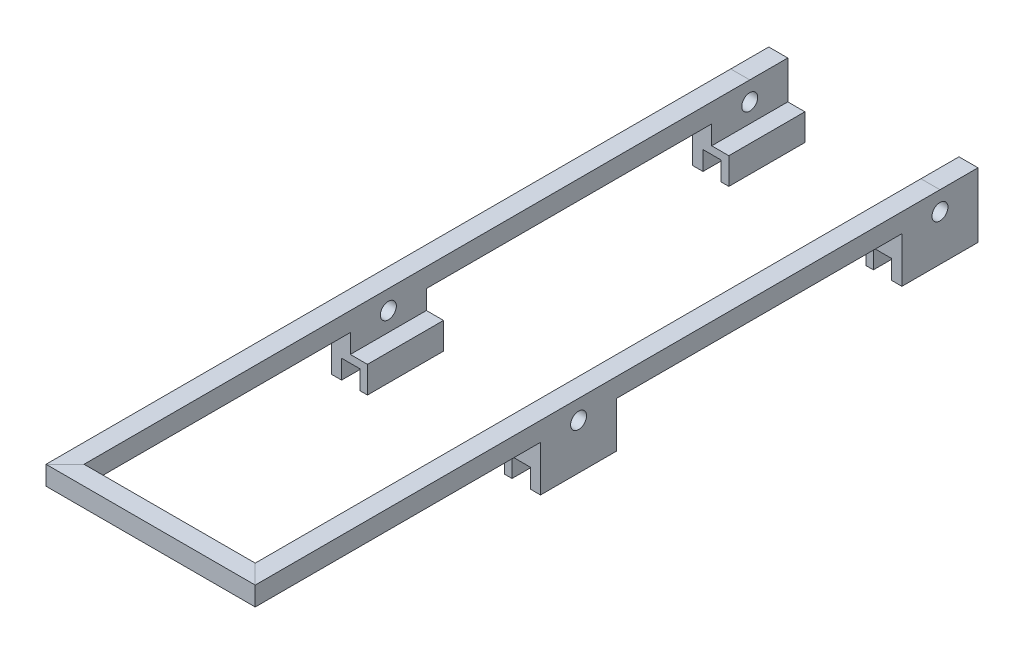
SolidWorks part; units mm, degrees
ref_plane "Front Plane" through (0, 0, 0) normal (0, 0, 1) x (1, 0, 0)
ref_plane "Top Plane" through (0, 0, 0) normal (0, 1, 0) x (1, 0, 0)
ref_plane "Right Plane" through (0, 0, 0) normal (1, 0, 0) x (0, 0, -1)
sketch "rail_path" plane through (0, 0, 0) normal (0, 1, 0) x (1, 0, 0)
  line L0 (28.575, 111.125) -> (28.575, 123.825)
  line L1 (-28.575, -111.125) -> (28.575, -111.125)
  line L2 (-28.575, -111.125) -> (-28.575, 111.125)
  line L3 (-28.575, 111.125) -> (28.575, 111.125) construction
  line L4 (28.575, -111.125) -> (28.575, 111.125)
  line L5 (-28.575, -111.125) -> (28.575, 111.125) construction
  line L6 (-28.575, 111.125) -> (28.575, -111.125) construction
  line L7 (-28.575, 111.125) -> (-28.575, 123.825)
  point P0 (0, 0)
  dimension "D1" = 222.25
  dimension "D2" = 57.15
  dimension "D3" = 12.7
  dimension "D4" = 12.7
sketch "rail_profile" plane through (0, 0, 0) normal (0, 0, 1) x (1, 0, 0)
  line L0 (-28.575, 0) -> (28.575, 0) construction
  line L1 (28.575, 0) -> (34.925, 0)
  line L2 (28.575, 0) -> (28.575, 6.35)
  line L3 (28.575, 6.35) -> (34.925, 6.35)
  line L4 (34.925, 0) -> (34.925, 6.35)
  line L5 (-28.575, 0) -> (28.575, 0) construction
  point P8 (0, 0)
  point P9 (0, 0)
  point P10 (0, 0)
  dimension "D1" = 6.35
  dimension "D2" = 6.35
sweep "Sweep1" add profiles "rail_profile" path "rail_path"
sketch "clip_profile" plane through (0, 0, 0) normal (0, 0, 1) x (1, 0, 0)
  line L2 (34.925, 0) -> (28.575, 0)
  line L4 (28.575, 0) -> (-28.575, 0)
  line L12 (-28.575, 6.35) -> (28.575, 6.35)
  line L16 (28.575, 0) -> (28.575, -6.35)
  line L18 (34.925, 0) -> (34.925, -6.35)
  line L19 (28.575, -6.35) -> (34.925, -6.35) construction
  line L30 (34.925, -6.35) -> (28.575, -6.35) construction
  line L31 (28.575, -6.35) -> (22.86, -6.35)
  line L33 (34.925, -6.35) -> (34.925, -15.24)
  line L34 (34.925, -15.24) -> (31.496, -15.24)
  line L35 (22.86, -6.35) -> (22.86, -15.24)
  line L37 (25.4, -15.24) -> (25.4, -8.89)
  line L38 (25.4, -8.89) -> (31.496, -8.89)
  line L39 (31.496, -15.24) -> (31.496, -8.89)
  line L40 (31.496, -15.24) -> (25.4, -15.24) construction
  line L41 (25.4, -15.24) -> (22.86, -15.24)
  line L42 (34.925, 6.35) -> (34.925, 0)
  line L43 (34.925, 0) -> (28.575, 0)
  line L45 (-28.575, 0) -> (-34.925, 0)
  line L46 (-34.925, 0) -> (-34.925, 6.35)
  line L47 (-34.925, 6.35) -> (-28.575, 6.35)
  line L49 (28.575, 6.35) -> (34.925, 6.35)
  point P1 (0, 0)
  point P12 (0, 0)
  point P21 (0, 0)
  dimension "D1" = 6.35
  dimension "D2" = 6.096
  dimension "D4" = 6.35
  dimension "D5" = 8.89
  dimension "D6" = 6.35
  dimension "D7" = 3.175
  dimension "D3" = 2.54
ref_plane "FrontClipPlane" through (0, 0, -111.125) normal (0, 0, -1) x (-1, 0, 0)
ref_plane "BackClipPlane" through (0, 0, 9.525) normal (0, 0, -1) x (-1, 0, 0)
sketch "BackClipProfile" plane through (0, 0, 9.525) normal (0, 0, -1) x (-1, 0, 0)
  line L0 (-34.925, 0) -> (-28.575, 0) construction
  line L1 (-28.575, -6.35) -> (-22.86, -6.35) construction
  line L2 (-22.86, -6.35) -> (-22.86, -15.24) construction
  line L3 (-25.4, -15.24) -> (-22.86, -15.24) construction
  line L4 (-25.4, -15.24) -> (-25.4, -8.89) construction
  line L5 (-25.4, -8.89) -> (-31.496, -8.89) construction
  line L6 (-31.496, -15.24) -> (-31.496, -8.89) construction
  line L7 (-34.925, -15.24) -> (-31.496, -15.24) construction
  line L8 (-34.925, -6.35) -> (-34.925, -15.24) construction
  line L10 (-28.575, 0) -> (-28.575, -6.35) construction
  line L11 (-34.925, 0) -> (-34.925, -6.35) construction
  line L12 (-34.925, 0) -> (-28.575, 0)
  line L13 (-28.575, -6.35) -> (-22.86, -6.35)
  line L14 (-22.86, -6.35) -> (-22.86, -15.24)
  line L15 (-25.4, -15.24) -> (-22.86, -15.24)
  line L16 (-25.4, -15.24) -> (-25.4, -8.89)
  line L17 (-25.4, -8.89) -> (-31.496, -8.89)
  line L18 (-31.496, -15.24) -> (-31.496, -8.89)
  line L19 (-34.925, -15.24) -> (-31.496, -15.24)
  line L20 (-34.925, -6.35) -> (-34.925, -15.24)
  line L22 (-28.575, 0) -> (-28.575, -6.35)
  line L23 (-34.925, 0) -> (-34.925, -6.35)
sketch "FrontClipProfile" plane through (0, 0, -111.125) normal (0, 0, -1) x (-1, 0, 0)
  line L0 (-34.925, -15.24) -> (-31.496, -15.24) construction
  line L1 (-31.496, -15.24) -> (-31.496, -8.89) construction
  line L2 (-25.4, -8.89) -> (-31.496, -8.89) construction
  line L3 (-25.4, -15.24) -> (-25.4, -8.89) construction
  line L4 (-25.4, -15.24) -> (-22.86, -15.24) construction
  line L5 (-22.86, -6.35) -> (-22.86, -15.24) construction
  line L6 (-28.575, -6.35) -> (-22.86, -6.35) construction
  line L8 (-34.925, -6.35) -> (-34.925, -15.24) construction
  line L9 (-28.575, 0) -> (-28.575, -6.35) construction
  line L10 (-34.925, 0) -> (-34.925, -6.35) construction
  line L11 (-34.925, 0) -> (-28.575, 0) construction
  line L12 (-34.925, -15.24) -> (-31.496, -15.24)
  line L13 (-31.496, -15.24) -> (-31.496, -8.89)
  line L14 (-25.4, -8.89) -> (-31.496, -8.89)
  line L15 (-25.4, -15.24) -> (-25.4, -8.89)
  line L16 (-25.4, -15.24) -> (-22.86, -15.24)
  line L17 (-22.86, -6.35) -> (-22.86, -15.24)
  line L18 (-28.575, -6.35) -> (-22.86, -6.35)
  line L20 (-34.925, -6.35) -> (-34.925, -15.24)
  line L21 (-28.575, 0) -> (-28.575, -6.35)
  line L22 (-34.925, 0) -> (-34.925, -6.35)
  line L23 (-34.925, 0) -> (-28.575, 0)
extrude "BackClip" add sketch "BackClipProfile" along normal mid plane 25.4
mirror "BackClipMirror" about plane through (0, 0, 0) normal (1, 0, 0) of "BackClip"
extrude "FrontClip" add sketch "FrontClipProfile" along normal mid plane 25.4
mirror "FrontClipMirror" about plane through (0, 0, 0) normal (1, 0, 0) of "FrontClip"
sketch "Sketch8" plane through (28.575, 0, 0) normal (-1, 0, 0) x (0, 0, 1)
  line L0 (-123.825, 6.35) -> (-123.825, -6.35) construction
  line L1 (-123.825, -6.35) -> (-98.425, -6.35) construction
  line L2 (-98.425, -6.35) -> (-98.425, 0) construction
  line L9 (111.125, 6.35) -> (-111.125, 6.35) construction
  line L12 (-111.125, 6.35) -> (-123.825, 6.35) construction
  line L13 (-98.425, -6.35) -> (-98.425, 0) construction
  line L14 (-123.825, -6.35) -> (-98.425, -6.35) construction
  line L15 (-111.125, 6.35) -> (-123.825, 6.35) construction
  line L16 (-123.825, 6.35) -> (-123.825, -6.35) construction
  line L17 (111.125, 6.35) -> (-111.125, 6.35) construction
  line L18 (-123.825, 6.35) -> (-98.425, -6.35) construction
  line L19 (22.225, -6.35) -> (22.225, 0) construction
  line L20 (-3.175, -6.35) -> (22.225, -6.35) construction
  line L21 (-3.175, -6.35) -> (-3.175, 0) construction
  line L22 (22.225, -6.35) -> (22.225, 0) construction
  line L23 (-3.175, -6.35) -> (22.225, -6.35) construction
  line L24 (-3.175, -6.35) -> (-3.175, 0) construction
  line L25 (-3.175, -6.35) -> (22.225, 6.35) construction
  circle A0 centre (-111.125, 0) radius 2.667
  circle A1 centre (9.525, 0) radius 2.667
  dimension "D1" = 5.334
  dimension "D2" = 5.334
extrude "Cut-Extrude1" cut sketch "Sketch8" against normal through all both and the other way through all
equation "\"rail_horizontal_clearance\"= 0.25 / 2"
